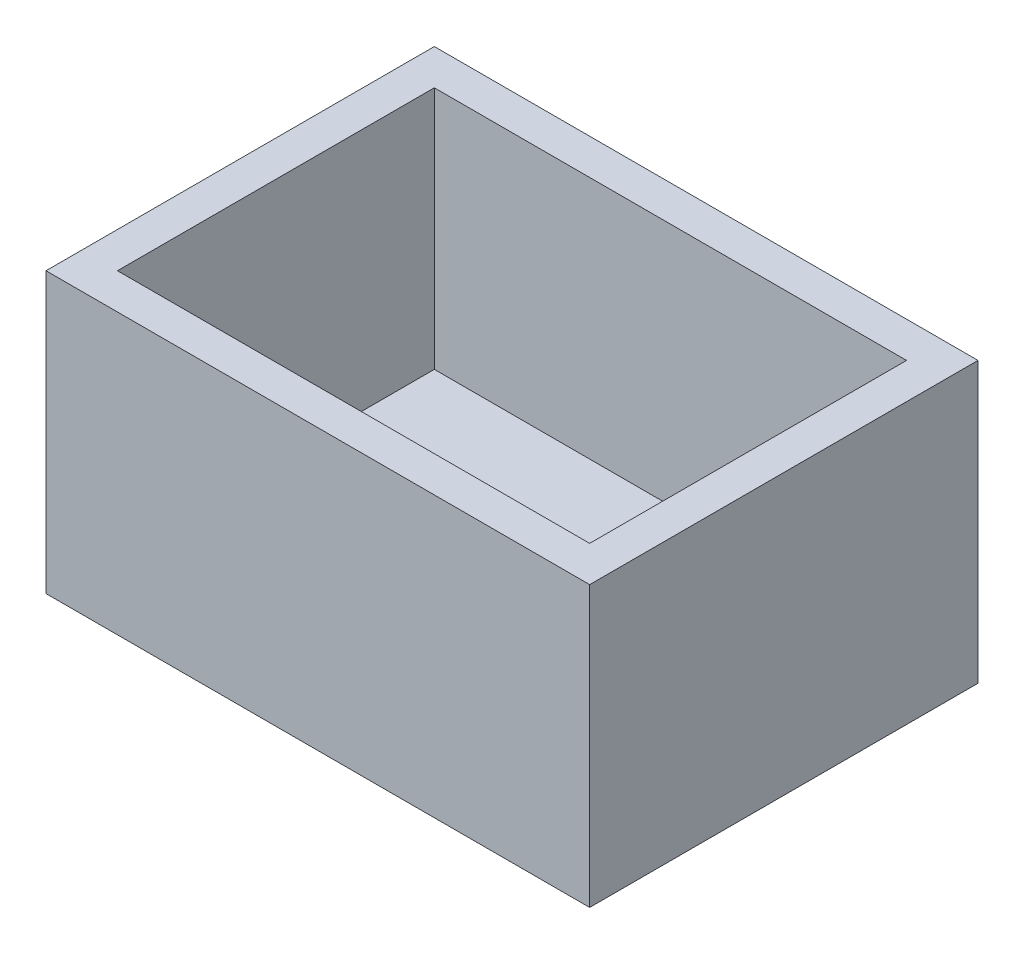
SolidWorks part; units mm, degrees
ref_plane "Front Plane" through (0, 0, 0) normal (0, 0, 1) x (1, 0, 0)
ref_plane "Top Plane" through (0, 0, 0) normal (0, 1, 0) x (1, 0, 0)
ref_plane "Right Plane" through (0, 0, 0) normal (1, 0, 0) x (0, 0, -1)
sketch "Sketch1" plane through (0, 0, 0) normal (0, 1, 0) x (1, 0, 0)
  line L1 (0, 0) -> (35, 0)
  line L2 (0, 0) -> (0, 25)
  line L3 (0, 25) -> (35, 25)
  line L4 (35, 0) -> (35, 25)
  dimension "D1" = 35
  dimension "D2" = 25
extrude "Boss-Extrude1" add sketch "Sketch1" along normal blind 18
shell "Shell1" thickness 2.3 removed face at (17.5, 18, -12.5)
